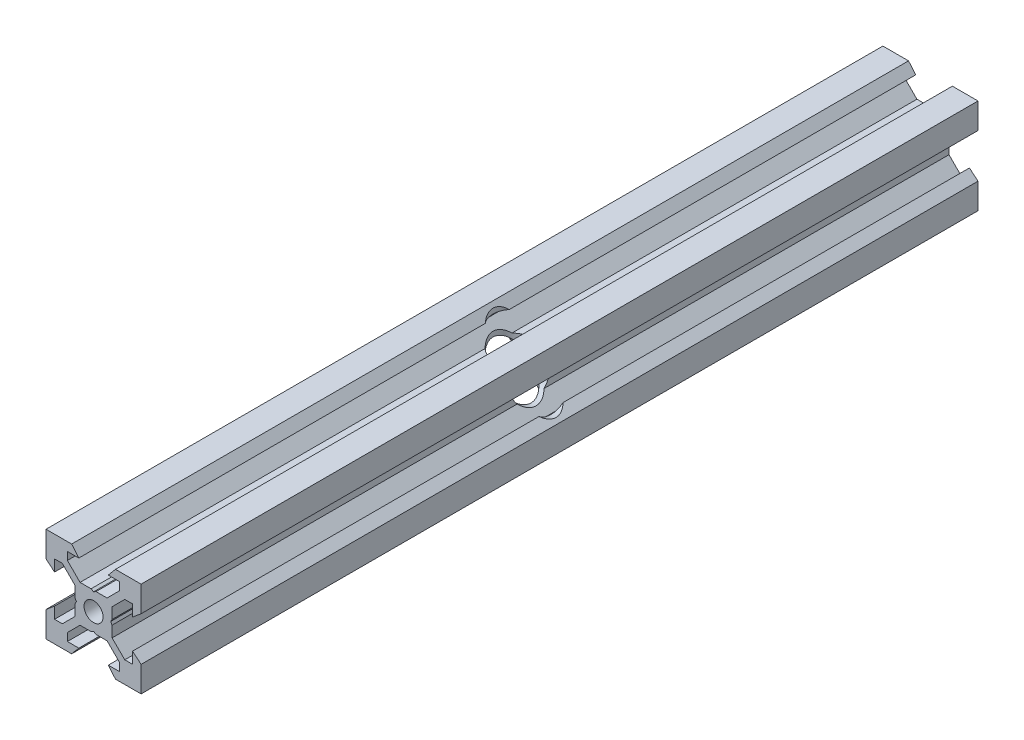
SolidWorks part; units mm, degrees
material "3.3535 (EN-AW 5754)"
ref_plane "Front Plane" through (0, 0, 0) normal (0, 0, 1) x (1, 0, 0)
ref_plane "Top Plane" through (0, 0, 0) normal (0, 1, 0) x (1, 0, 0)
ref_plane "Right Plane" through (0, 0, 0) normal (1, 0, 0) x (0, 0, -1)
sketch "Sketch1" plane through (0, 0, 0) normal (0, 0, 1) x (1, 0, 0)
  line L0 (10, 10) -> (4.6104, 10) construction
  line L1 (10, 10) -> (10, 4.6104) construction
  line L2 (10, -10) -> (10, -4.6104) construction
  line L3 (10, -10) -> (4.6104, -10) construction
  line L4 (10, 10) -> (10, 4.6104)
  line L5 (6.5607, 5.5) -> (8.2, 5.5)
  line L6 (5.5, 8.2) -> (5.5, 6.5607)
  line L7 (10, 10) -> (4.6104, 10)
  line L8 (10, 10) -> (10, 4.6104)
  line L9 (6.5607, 5.5) -> (3.9, 2.8393)
  line L10 (5.5, 6.5607) -> (2.8393, 3.9)
  line L11 (10, 4.6104) -> (8.2, 3.1)
  line L12 (4.6104, 10) -> (3.1, 8.2)
  line L13 (8.2, 3.1) -> (8.2, 5.5)
  line L14 (3.1, 8.2) -> (5.5, 8.2)
  line L15 (-6.5607, 5.5) -> (-8.2, 5.5)
  line L16 (6.5607, -5.5) -> (8.2, -5.5)
  line L17 (3.1, -8.2) -> (5.5, -8.2)
  line L18 (8.2, -3.1) -> (8.2, -5.5)
  line L19 (4.6104, -10) -> (3.1, -8.2)
  line L20 (10, -4.6104) -> (8.2, -3.1)
  line L21 (0.5196, -3.9) -> (0, -3.6)
  line L22 (0.5196, 3.9) -> (0, 3.6)
  line L23 (3.6, 0) -> (3.9, -0.5196)
  line L24 (3.9, 0.5196) -> (3.6, 0)
  line L25 (3.9, 0.5196) -> (3.9, 2.8393)
  line L26 (2.8393, 3.9) -> (0.5196, 3.9)
  line L27 (3.9, -2.8393) -> (3.9, -0.5196)
  line L28 (2.8393, -3.9) -> (0.5196, -3.9)
  line L29 (5.5, -6.5607) -> (2.8393, -3.9)
  line L30 (6.5607, -5.5) -> (3.9, -2.8393)
  line L31 (10, -10) -> (10, -4.6104)
  line L32 (10, -10) -> (4.6104, -10)
  line L33 (5.5, -8.2) -> (5.5, -6.5607)
  line L34 (-6.5607, -5.5) -> (-8.2, -5.5)
  line L35 (10, -10) -> (10, -4.6104)
  line L36 (0, 0) -> (0, 8.2) construction
  line L37 (-10, -10) -> (-4.6104, -10) construction
  line L38 (-10, -10) -> (-10, -4.6104) construction
  line L39 (-10, 10) -> (-10, 4.6104) construction
  line L40 (-10, 10) -> (-4.6104, 10) construction
  line L41 (-10, -10) -> (-10, -4.6104)
  line L43 (-5.5, -8.2) -> (-5.5, -6.5607)
  line L44 (-10, -10) -> (-4.6104, -10)
  line L45 (-10, -10) -> (-10, -4.6104)
  line L46 (-6.5607, -5.5) -> (-3.9, -2.8393)
  line L47 (-5.5, -6.5607) -> (-2.8393, -3.9)
  line L48 (-2.8393, -3.9) -> (-0.5196, -3.9)
  line L49 (-3.9, -2.8393) -> (-3.9, -0.5196)
  line L50 (-2.8393, 3.9) -> (-0.5196, 3.9)
  line L51 (-3.9, 0.5196) -> (-3.9, 2.8393)
  line L52 (-3.9, 0.5196) -> (-3.6, 0)
  line L53 (-3.6, 0) -> (-3.9, -0.5196)
  line L54 (-0.5196, 3.9) -> (0, 3.6)
  line L55 (-0.5196, -3.9) -> (0, -3.6)
  line L56 (-10, -4.6104) -> (-8.2, -3.1)
  line L57 (-4.6104, -10) -> (-3.1, -8.2)
  line L58 (-8.2, -3.1) -> (-8.2, -5.5)
  line L59 (-3.1, -8.2) -> (-5.5, -8.2)
  line L60 (-10, -10) -> (10, -10) construction
  line L61 (-10, -10) -> (-10, 10) construction
  line L62 (-3.1, 8.2) -> (-5.5, 8.2)
  line L63 (-8.2, 3.1) -> (-8.2, 5.5)
  line L64 (-4.6104, 10) -> (-3.1, 8.2)
  line L65 (-10, 4.6104) -> (-8.2, 3.1)
  line L66 (-5.5, 6.5607) -> (-2.8393, 3.9)
  line L67 (-6.5607, 5.5) -> (-3.9, 2.8393)
  line L68 (-10, 10) -> (-10, 4.6104)
  line L69 (-10, 10) -> (-4.6104, 10)
  line L70 (-5.5, 8.2) -> (-5.5, 6.5607)
  line L71 (-10, 10) -> (10, 10) construction
  line L72 (-10, 10) -> (-10, 4.6104)
  line L73 (10, -10) -> (10, 10) construction
  line L74 (-10, -10) -> (10, 10) construction
  line L75 (-10, 10) -> (10, -10) construction
  circle A0 centre (0, 0) radius 2
  dimension "D7" = 4
  dimension "D1" = 20
  dimension "D2" = 5.3896
  dimension "D3" = 4.5
  dimension "D4" = 50
  dimension "D5" = 1.8
  dimension "D6" = 1.5104
  dimension "D8" = 5.5
  dimension "D9" = 120
  dimension "D10" = 0.3
  dimension "D11" = 2.3197
  dimension "D12" = 7.8
  dimension "D13" = 7.8
  dimension "D14" = 1.5
  dimension "D15" = 2.6607
extrude "Boss-Extrude1" add sketch "Sketch1" along normal blind 176 contours L70 L62 L64 L69 L68 L65 L63 L15 L67 L51 L52 L53 L49 L46 L34 L58 L56 L41 L44 L57 L59 L43 L47 L48 L55 L21 L28 L29 L33 L17 L19 L32 L31 L20 L18 L16 L30 L27 L23 L24 L25 L9 L5 L13 L11 L4 L7 L12 L14 L6 L10 region at (9.7172, 7.3052, 0)
sketch "Sketch4" plane through (0, 0, 0) normal (1, 0, 0) x (0, 0, -1)
  line L0 (-176, 0) -> (0, 0) construction
  circle A0 centre (-88, 0) radius 4
  dimension "D1" = 8
extrude "Cut-Extrude1" cut sketch "Sketch4" against normal through all both and the other way through all
sketch "Sketch5" plane through (0, 0, 0) normal (0, 1, 0) x (1, 0, 0)
  line L0 (0, 0) -> (0, -176) construction
  circle A0 centre (0, -88) radius 4
  dimension "D1" = 8
extrude "Cut-Extrude2" cut sketch "Sketch5" against normal through all both and the other way through all
